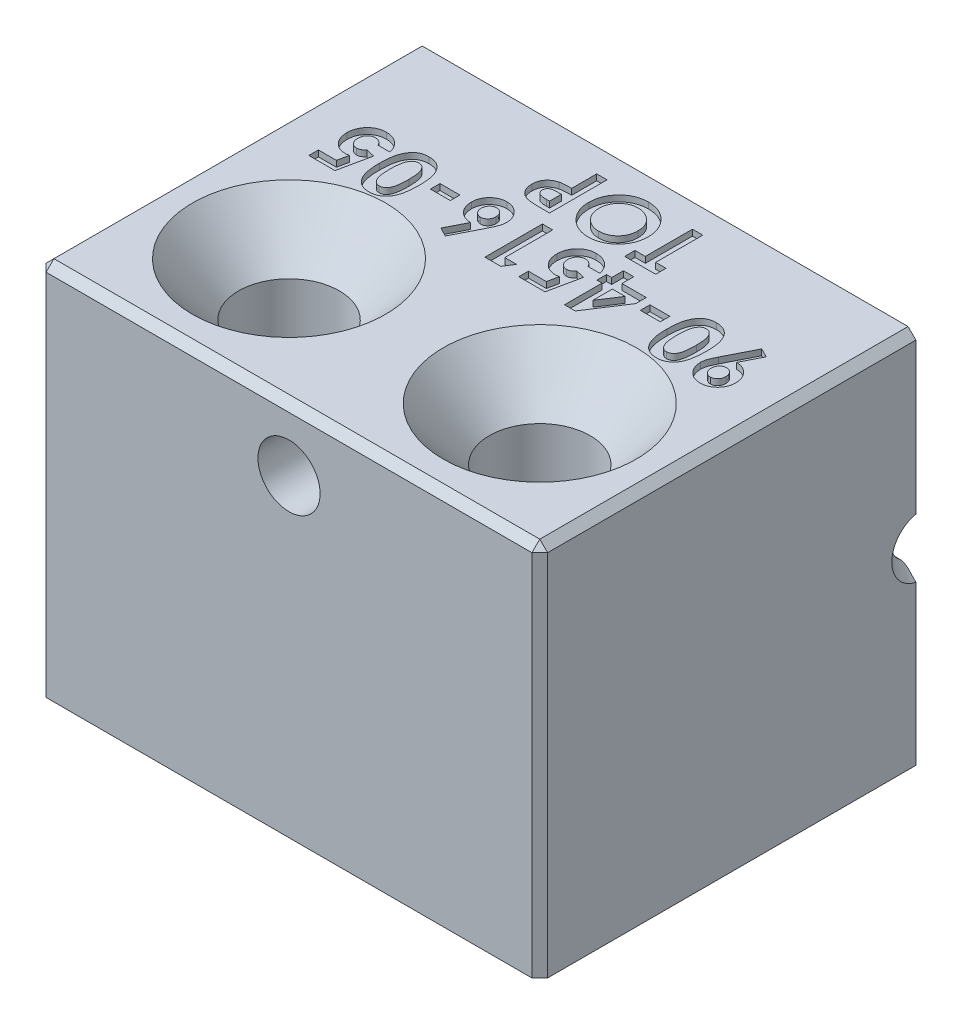
SolidWorks part; units mm, degrees
material "A-2 Steel"
ref_plane "Alzado" through (0, 0, 0) normal (0, 0, 1) x (1, 0, 0)
ref_plane "Planta" through (0, 0, 0) normal (0, 1, 0) x (1, 0, 0)
ref_plane "Vista lateral" through (0, 0, 0) normal (1, 0, 0) x (0, 0, -1)
sketch "Croquis1" plane through (0, 0, 0) normal (0, 1, 0) x (1, 0, 0)
  line L1 (12.7, 9.525) -> (-12.7, 9.525)
  line L2 (12.7, 9.525) -> (12.7, -9.525)
  line L3 (12.7, -9.525) -> (-12.7, -9.525)
  line L4 (-12.7, 9.525) -> (-12.7, -9.525)
  line L5 (0, -9.525) -> (0, 9.525) construction
  line L6 (12.7, 0) -> (-12.7, 0) construction
  point P64 (0, 0)
  dimension "D1" = 19.05
  dimension "D2" = 25.4
extrude "Saliente-Extruir1" add sketch "Croquis1" along normal blind 19.05
sketch "Croquis3" plane through (0, 19.05, 0) normal (0, 1, 0) x (1, 0, 0)
  line L0 (6.35, -3.175) -> (-6.35, -3.175) construction
  line L2 (0, 0) -> (0, -3.175) construction
  line L4 (-12.7, -9.525) -> (12.7, -9.525) construction
  point P0 (-6.35, -3.175)
  point P2 (6.35, -3.175)
  dimension "D1" = 6.35
  dimension "D2" = 12.7
hole_wizard "Avellanado para tornillo con cabeza ovalada de #101" positions "Croquis3" profile "Croquis4" countersink size "#10" standard "Ansi Inch" end condition through all
sketch "Croquis4" plane through (-6.35, 19.05, 3.175) normal (1, 0, 0) x (0, 0, 1)
  line L0 (0, 0) -> (0, 19.05)
  line L1 (0, 19.05) -> (2.5527, 19.05)
  line L2 (2.5527, 19.05) -> (2.5527, 2.6882)
  line L3 (2.5527, 2.6882) -> (4.8895, 0)
  line L5 (4.8895, 0) -> (0, 0)
  line L6 (-2.5527, 2.6882) -> (-4.8895, 0) construction
  line L11 (0, -6.35) -> (0, 107.95) construction
  dimension "Diámetro de taladro hasta el siguiente" = 5.1054
  dimension "Profundidad de taladro hasta el siguiente" = 19.05
  dimension "Diámetro de avellanado cercano" = 9.779
  dimension "Ángulo de avellanado cercano" = 82
sketch "Croquis6" plane through (-12.7, 0, 0) normal (1, 0, 0) x (0, 0, -1)
  line L0 (9.525, 19.05) -> (9.525, 0) construction
  circle A0 centre (9.525, 9.525) radius 7.112
  dimension "D1" = 14.224
extrude "Cortar-Extruir2" cut sketch "Croquis6" along normal blind 6.35 draft 45
sketch "Croquis8" plane through (12.7, 0, 0) normal (1, 0, 0) x (0, 0, -1)
  line L1 (9.8298, 9.525) -> (9.525, 9.525) construction
  line L2 (9.525, 19.05) -> (9.525, 0) construction
  circle A0 centre (9.8298, 9.525) radius 0.8636
  dimension "D1" = 1.7272
  dimension "D2" = 0.3048
extrude "Cortar-Extruir3" cut sketch "Croquis8" against normal through all
fillet "Redondeo1" radius 0.508 2 edges at (3.152, 8.717, -9.525) (3.152, 10.333, -9.525)
sketch "Croquis9" plane through (0, 0, 9.525) normal (0, 0, 1) x (1, 0, 0)
  line L0 (0, 19.05) -> (0, 15.875) construction
  line L1 (-12.7, 19.05) -> (12.7, 19.05) construction
  point P0 (0, 15.875)
  dimension "D1" = 3.175
chamfer "Chaflán3" distance 0.6604 angle 45 1 edges at (12.7, 9.525, -8.9662) tangent propagation no
hole_wizard "Taladros de espiga de 1/8 (0.124)2" positions "Croquis9" profile "Croquis10" hole size "1/8" standard "Ansi Inch" end condition through all
sketch "Croquis10" plane through (0, 15.875, 9.525) normal (1, 0, 0) x (0, -1, 0)
  line L0 (0, 0) -> (0, 19.05)
  line L1 (0, 19.05) -> (1.5748, 19.05)
  line L2 (1.5748, 19.05) -> (1.5748, 0)
  line L5 (1.5748, 0) -> (0, 0)
  line L11 (0, -6.35) -> (0, 107.95) construction
  dimension "Diámetro de taladro hasta el siguiente" = 3.1496
  dimension "Profundidad de taladro hasta el siguiente" = 19.05
sketch "Croquis11" plane through (0, 19.05, 0) normal (0, 1, 0) x (1, 0, 0)
  line L0 (12.7, 4.7625) -> (-12.7, 4.7625) construction
  line L1 (5.7224, 8.3344) -> (-5.7224, 8.3344) construction
  line L2 (0, 4.7625) -> (0, 8.3344) construction
  line L4 (0, 0) -> (0, 4.7625) construction
  text T0 "90-4516-05\r\n" font "Century Gothic" height in points 11
  text T1 "TOP" font "Century Gothic" height in points 11
  dimension "D1" = 4.7625
  dimension "D2" = 3.5719
  dimension "D3" = 25.4
extrude "Cortar-Extruir4" cut sketch "Croquis11" against normal blind 0.3048
chamfer "Chaflán4" distance 0.3969 angle 45 5 edges at (-12.7, 9.525, 9.525) (12.7, 9.525, 9.525) (12.7, 19.05, 0) (0, 19.05, 9.525) (-12.7, 19.05, 0)
